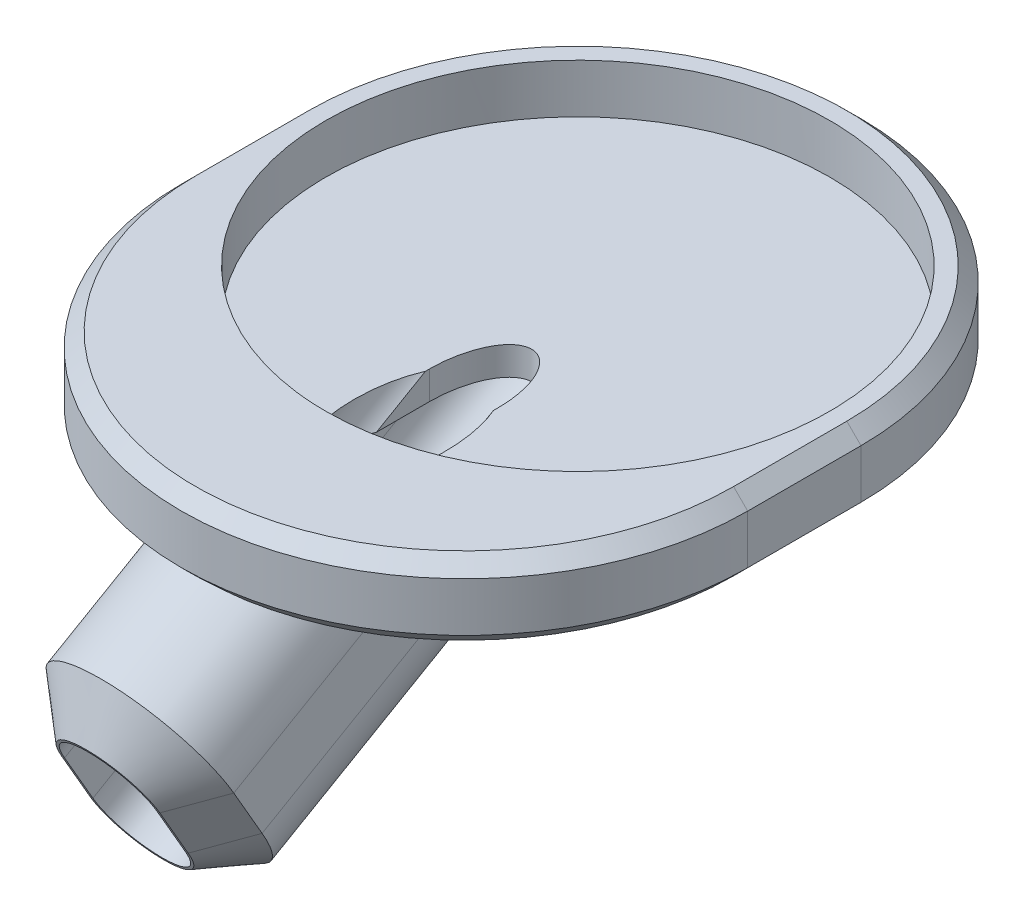
SolidWorks part; units mm, degrees
ref_plane "Front Plane" through (0, 0, 0) normal (0, 0, 1) x (1, 0, 0)
ref_plane "Top Plane" through (0, 0, 0) normal (0, 1, 0) x (1, 0, 0)
ref_plane "Right Plane" through (0, 0, 0) normal (1, 0, 0) x (0, 0, -1)
sketch "Sketch1" plane through (0, 0, 0) normal (0, 1, 0) x (1, 0, 0)
  line L0 (0, 0) -> (0, -12.7) construction
  line L1 (31.75, 0) -> (31.75, -12.7)
  line L2 (-31.75, 0) -> (-31.75, -12.7)
  line L3 (0, -28.25) -> (0, -40.1082) construction
  line L4 (-2.5, -40.1082) -> (2.5, -40.1082) construction
  line L5 (-2.5, -40.1082) -> (-2.5, -28.1392)
  line L6 (2.5, -40.1082) -> (2.5, -28.1392)
  circle A0 centre (0, 0) radius 28.25
  arc A1 (31.75, 0) -> (-31.75, 0) centre (0, 0) ccw
  arc A2 (-31.75, -12.7) -> (31.75, -12.7) centre (0, -12.7) ccw
  arc A3 (-2.5, -40.1082) -> (2.5, -40.1082) centre (0, -40.1082) ccw
  point P3 (0, -6.35)
  point P6 (0, 0)
  point P15 (0, -40.1082)
  dimension "D1" = 56.5
  dimension "D2" = 63.5
  dimension "D3" = 12.7
  dimension "D4" = 5
extrude "Boss-Extrude1" add sketch "Sketch1" along normal blind 5.5 contours L2 A2 L1 A1 A3 L5 A0 L6 | L5 A3 L6 A0 region at (30.7581, 0, 6.35) region at (0, 0, 35.1536)
extrude "Boss-Extrude2" add sketch "Sketch1<3>" against normal blind 3.175 contours L2 A2 L1 A1
sketch "Sketch1<3>" plane through (0, 0, 0) normal (0, 1, 0) x (1, 0, 0) same geometry as "Sketch1"
ref_plane "Plane5" through (0, -18.6869, 52.3667) normal (0, 0.5, -0.866) x (1, 0, 0)
sketch "Sketch9" plane through (0, -18.6869, 52.3667) normal (0, 0.5, -0.866) x (1, 0, 0)
  line L0 (0, 6.35) -> (0, 0) construction
  line L1 (5.18, 6.35) -> (5.18, 0)
  line L2 (-3.81, 6.35) -> (-3.81, 0)
  line L3 (3.81, 0) -> (3.81, 6.35)
  line L4 (-3.81, 6.35) -> (-3.81, 0) construction
  line L5 (3.81, 0) -> (3.81, 6.35) construction
  line L6 (-5.08, 6.35) -> (-5.08, 0)
  line L7 (5.08, 0) -> (5.08, 6.35)
  line L8 (-5.08, 6.35) -> (-5.08, 0) construction
  line L9 (5.08, 0) -> (5.08, 6.35) construction
  line L10 (-5.18, 6.35) -> (-5.18, 0)
  line L11 (0, 6.35) -> (0, 0) construction
  line L12 (9.9425, 6.35) -> (9.9425, 0)
  line L13 (-9.9425, 6.35) -> (-9.9425, 0)
  arc A0 (5.18, 6.35) -> (-5.18, 6.35) centre (0, 6.35) ccw
  arc A1 (-5.18, 0) -> (5.18, 0) centre (0, 0) ccw
  arc A2 (3.81, 6.35) -> (-3.81, 6.35) centre (0, 6.35) ccw
  arc A3 (-3.81, 0) -> (3.81, 0) centre (0, 0) ccw
  arc A4 (3.81, 6.35) -> (-3.81, 6.35) centre (0, 6.35) ccw construction
  arc A5 (-3.81, 0) -> (3.81, 0) centre (0, 0) ccw construction
  arc A6 (5.08, 6.35) -> (-5.08, 6.35) centre (0, 6.35) ccw
  arc A7 (-5.08, 0) -> (5.08, 0) centre (0, 0) ccw
  arc A8 (5.08, 6.35) -> (-5.08, 6.35) centre (0, 6.35) ccw construction
  arc A9 (-5.08, 0) -> (5.08, 0) centre (0, 0) ccw construction
  arc A10 (9.9425, 6.35) -> (-9.9425, 6.35) centre (0, 6.35) ccw
  arc A11 (-9.9425, 0) -> (9.9425, 0) centre (0, 0) ccw
  point P8 (0, 3.175)
  point P17 (0, 3.175)
  dimension "D3" = 0.1
  dimension "D4" = 1.27
  dimension "D5" = 4.7625
  dimension "D1" = 0
  dimension "D2" = 0
extrude "Boss-Extrude4" add sketch "Sketch9" along normal up to next
extrude "Cut-Extrude1" cut sketch "Sketch1<5>" against normal blind 12.7 and the other way blind 2.54 contours L5 A3 L6 A0 region at (0, 0, 35.1536)
sketch "Sketch1<5>" plane through (0, 0, 0) normal (0, 1, 0) x (1, 0, 0) same geometry as "Sketch1"
sketch "Sketch6" plane through (0, -3.175, 0) normal (0, -1, 0) x (1, 0, 0)
  line L0 (3.81, 12.7993) -> (3.81, 25.4993) construction
  line L1 (-3.81, 25.4993) -> (-3.81, 12.7993) construction
  line L2 (3.81, 12.7993) -> (3.81, 25.4993)
  line L3 (-3.81, 25.4993) -> (-3.81, 12.7993)
  ellipse E0 centre (0, 25.4993) end of major axis (0, 33.1193) minor radius 3.81 (3.81, 25.4993) -> (-3.81, 25.4993) ccw construction
  ellipse E1 centre (0, 12.7993) end of major axis (0, 20.4193) minor radius 3.81 (-3.81, 12.7993) -> (3.81, 12.7993) ccw construction
  ellipse E2 centre (0, 25.4993) end of major axis (0, 33.1193) minor radius 3.81 (3.81, 25.4993) -> (-3.81, 25.4993) ccw
  ellipse E3 centre (0, 12.7993) end of major axis (0, 20.4193) minor radius 3.81 (-3.81, 12.7993) -> (3.81, 12.7993) ccw
extrude "Cut-Extrude2" cut sketch "Sketch6" against normal up to surface (5.715 mm away) contours L3 E3 L2 E2 region at (0, -3.175, 19.1493) up to face at (0, 2.54, 34.7764)
ref_plane "Plane1" through (0, -16.2347, 28.1193) normal (0, 0.5, -0.866) x (-1, 0, 0)
ref_plane "Plane2" through (0, -3.5347, 6.1222) normal (0, 0.5, -0.866) x (-1, 0, 0)
sketch "Sketch7" plane through (0, -3.5347, 6.1222) normal (0, 0.5, -0.866) x (-1, 0, 0)
  circle A0 centre (0, 10) radius 5.08
  circle A1 centre (0, 10) radius 3.175
  circle A2 centre (0, 10) radius 3.175 construction
  dimension "D2" = 10.16
  dimension "D1" = 0
extrude "Cut-Extrude4" cut sketch "Sketch7" against normal blind 19.05
chamfer "Chamfer3" distance 4.445 angle 45 4 edges at (0, -10.0765, 57.3379) (9.9425, -21.4365, 50.7792) (-9.9425, -21.4365, 50.7792) (0, -32.7966, 44.2204)
chamfer "Chamfer4" distance 1.5875 angle 45 8 edges at (-23.5766, -3.175, 33.9651) (31.75, -3.175, 6.35) (-31.75, -3.175, 6.35) (0, -3.175, -31.75) (0, 5.5, -31.75) (-31.75, 5.5, 6.35) (31.75, 5.5, 6.35) (0, 5.5, 44.45)
